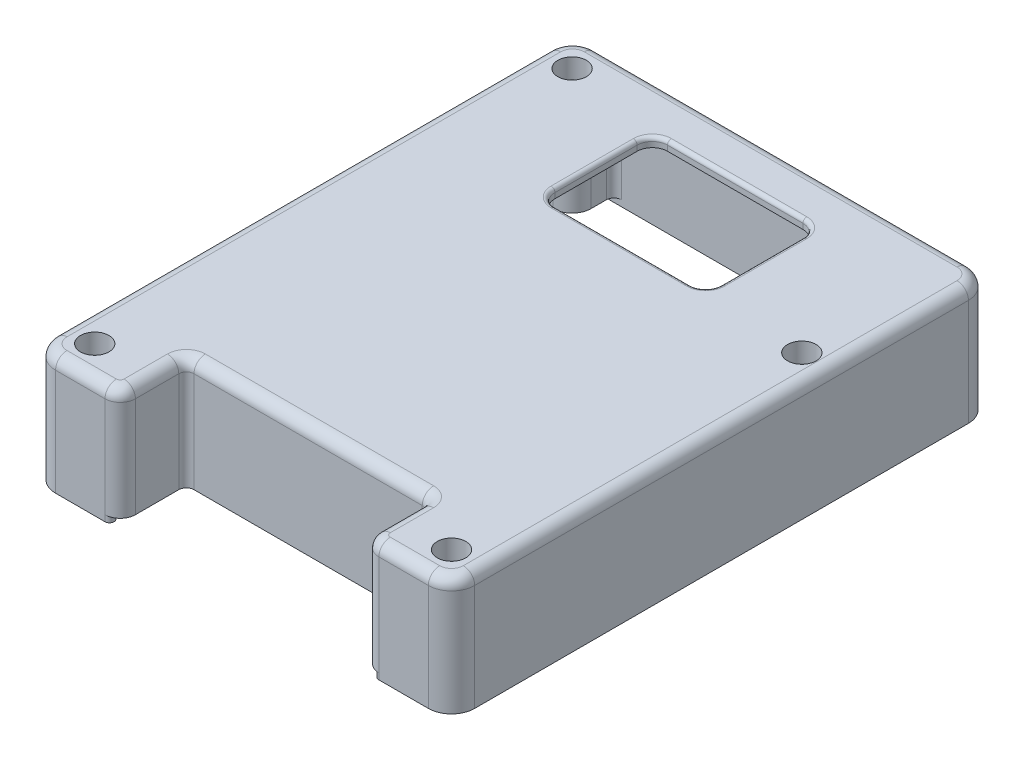
SolidWorks part; units mm, degrees
ref_plane "Front Plane" through (0, 0, 0) normal (0, 0, 1) x (1, 0, 0)
ref_plane "Top Plane" through (0, 0, 0) normal (0, 1, 0) x (1, 0, 0)
ref_plane "Right Plane" through (0, 0, 0) normal (1, 0, 0) x (0, 0, -1)
sketch "Esquisse1" plane through (0, 0, 0) normal (0, 1, 0) x (1, 0, 0)
  line L0 (-20.9, 31.3) -> (-20.9, 33.3)
  line L1 (-19.9, 34.3) -> (23.35, 34.3)
  line L2 (-26.35, 27.8) -> (-26.35, -27.9)
  line L3 (-19.95, -34.3) -> (-18.2, -34.3)
  line L4 (26.35, 31.3) -> (26.35, 17.55)
  line L5 (-26.35, 34.3) -> (26.35, -34.3) construction
  line L6 (-26.35, -34.3) -> (26.35, 34.3) construction
  line L7 (-24.5, 35.5) -> (24.5, 35.5)
  line L8 (-27.55, 32.45) -> (-27.55, -32.45)
  line L9 (-24.5, -35.5) -> (-18, -35.5)
  line L10 (27.55, 32.45) -> (27.55, -32.45)
  line L11 (-23.4, 28.8) -> (-25.35, 28.8)
  line L12 (20.95, -31.4) -> (20.95, -33.3)
  line L13 (23.45, -28.9) -> (25.35, -28.9)
  line L14 (-20.95, -31.4) -> (-20.95, -33.3)
  line L15 (-23.45, -28.9) -> (-25.35, -28.9)
  line L16 (24.05, 16.55) -> (25.35, 16.55)
  line L17 (24.05, 11.55) -> (25.35, 11.55)
  line L18 (26.35, 10.55) -> (26.35, -27.9)
  line L19 (0, 0) -> (0, -34.3) construction
  line L20 (0, -26.8) -> (15, -26.8)
  line L21 (0, -26.8) -> (-15, -26.8)
  line L22 (-16, -27.8) -> (-16, -33.5)
  line L23 (16, -27.8) -> (16, -33.5)
  line L24 (18, -35.5) -> (24.5, -35.5)
  line L25 (18.2, -34.3) -> (19.95, -34.3)
  line L26 (-17.2, -33.3) -> (-17.2, -26.6)
  line L27 (-16.2, -25.6) -> (16.2, -25.6)
  line L28 (17.2, -26.6) -> (17.2, -33.3)
  circle A0 centre (-23.45, -31.4) radius 1.1
  circle A1 centre (23.45, -31.4) radius 1.1
  circle A2 centre (-23.4, 31.3) radius 1.1
  circle A3 centre (24.05, 14.05) radius 1.1
  arc A4 (-23.4, 28.8) -> (-20.9, 31.3) centre (-23.4, 31.3) ccw
  arc A5 (-20.95, -31.4) -> (-23.45, -28.9) centre (-23.45, -31.4) ccw
  arc A6 (23.45, -28.9) -> (20.95, -31.4) centre (23.45, -31.4) ccw
  arc A7 (24.05, 16.55) -> (24.05, 11.55) centre (24.05, 14.05) ccw
  arc A8 (-27.55, -32.45) -> (-24.5, -35.5) centre (-24.5, -32.45) ccw
  arc A9 (24.5, -35.5) -> (27.55, -32.45) centre (24.5, -32.45) ccw
  arc A10 (24.5, 35.5) -> (27.55, 32.45) centre (24.5, 32.45) cw
  arc A11 (-24.5, 35.5) -> (-27.55, 32.45) centre (-24.5, 32.45) ccw
  arc A12 (23.35, 34.3) -> (26.35, 31.3) centre (23.35, 31.3) cw
  arc A13 (-25.35, 28.8) -> (-26.35, 27.8) centre (-25.35, 27.8) ccw
  arc A14 (-20.9, 33.3) -> (-19.9, 34.3) centre (-19.9, 33.3) cw
  arc A15 (25.35, -28.9) -> (26.35, -27.9) centre (25.35, -27.9) ccw
  arc A16 (20.95, -33.3) -> (19.95, -34.3) centre (19.95, -33.3) cw
  arc A17 (-20.95, -33.3) -> (-19.95, -34.3) centre (-19.95, -33.3) ccw
  arc A18 (-25.35, -28.9) -> (-26.35, -27.9) centre (-25.35, -27.9) cw
  arc A19 (25.35, 11.55) -> (26.35, 10.55) centre (25.35, 10.55) cw
  arc A20 (25.35, 16.55) -> (26.35, 17.55) centre (25.35, 17.55) ccw
  arc A21 (-17.2, -33.3) -> (-18.2, -34.3) centre (-18.2, -33.3) cw
  arc A22 (17.2, -33.3) -> (18.2, -34.3) centre (18.2, -33.3) ccw
  arc A23 (16, -33.5) -> (18, -35.5) centre (18, -33.5) ccw
  arc A24 (-16, -33.5) -> (-18, -35.5) centre (-18, -33.5) cw
  arc A25 (-17.2, -26.6) -> (-16.2, -25.6) centre (-16.2, -26.6) cw
  arc A26 (16.2, -25.6) -> (17.2, -26.6) centre (16.2, -26.6) cw
  arc A27 (15, -26.8) -> (16, -27.8) centre (15, -27.8) cw
  arc A28 (-15, -26.8) -> (-16, -27.8) centre (-15, -27.8) ccw
  point P0 (0, 0)
  point P59 (26.35, 11.55)
  point P79 (16, -35.5)
  dimension "D7" = 2.2
  dimension "D8" = 2.2
  dimension "D9" = 2.2
  dimension "D10" = 2.2
  dimension "D19" = 5
  dimension "D20" = 5
  dimension "D21" = 5
  dimension "D22" = 5
  dimension "D23" = 3.05
  dimension "D24" = 3
  dimension "D25" = 1
  dimension "D34" = 1
  dimension "D35" = 2
  dimension "D36" = 1
  dimension "D1" = 52.7
  dimension "D2" = 68.6
  dimension "D3" = 1.2
  dimension "D4" = 1.2
  dimension "D5" = 1.2
  dimension "D6" = 1.2
  dimension "D11" = 2.9
  dimension "D12" = 2.9
  dimension "D13" = 2.9
  dimension "D14" = 2.9
  dimension "D15" = 48.35
  dimension "D16" = 2.3
  dimension "D17" = 2.95
  dimension "D18" = 3
  dimension "D28" = 7.5
  dimension "D29" = 11.55
  dimension "D30" = 11.55
  dimension "D31" = 1.2
  dimension "D32" = 1.2
  dimension "D33" = 1.2
extrude "Boss.-Extru.1" add sketch "Esquisse1" along normal blind 13.5
sketch "Esquisse2" plane through (0, 13.5, 0) normal (0, 1, 0) x (1, 0, 0)
  line L16 (-24.5, -35.5) -> (-18, -35.5)
  line L17 (-16, -33.5) -> (-16, -27.8)
  line L18 (-15, -26.8) -> (15, -26.8)
  line L19 (16, -27.8) -> (16, -33.5)
  line L20 (18, -35.5) -> (24.5, -35.5)
  line L21 (27.55, -32.45) -> (27.55, 32.45)
  line L22 (24.5, 35.5) -> (-24.5, 35.5)
  line L23 (-27.55, 32.45) -> (-27.55, -32.45)
  line L24 (-24.5, -35.5) -> (-18, -35.5)
  line L25 (-16, -33.5) -> (-16, -27.8)
  line L26 (-15, -26.8) -> (15, -26.8)
  line L27 (16, -27.8) -> (16, -33.5)
  line L28 (18, -35.5) -> (24.5, -35.5)
  line L29 (27.55, -32.45) -> (27.55, 32.45)
  line L30 (24.5, 35.5) -> (-24.5, 35.5)
  line L31 (-27.55, 32.45) -> (-27.55, -32.45)
  arc A16 (-27.55, -32.45) -> (-24.5, -35.5) centre (-24.5, -32.45) ccw
  arc A17 (-18, -35.5) -> (-16, -33.5) centre (-18, -33.5) ccw
  arc A18 (-15, -26.8) -> (-16, -27.8) centre (-15, -27.8) ccw
  arc A19 (16, -27.8) -> (15, -26.8) centre (15, -27.8) ccw
  arc A20 (16, -33.5) -> (18, -35.5) centre (18, -33.5) ccw
  arc A21 (24.5, -35.5) -> (27.55, -32.45) centre (24.5, -32.45) ccw
  arc A22 (27.55, 32.45) -> (24.5, 35.5) centre (24.5, 32.45) ccw
  arc A23 (-24.5, 35.5) -> (-27.55, 32.45) centre (-24.5, 32.45) ccw
  arc A24 (-27.55, -32.45) -> (-24.5, -35.5) centre (-24.5, -32.45) ccw
  arc A25 (-18, -35.5) -> (-16, -33.5) centre (-18, -33.5) ccw
  arc A26 (-15, -26.8) -> (-16, -27.8) centre (-15, -27.8) ccw
  arc A27 (16, -27.8) -> (15, -26.8) centre (15, -27.8) ccw
  arc A28 (16, -33.5) -> (18, -35.5) centre (18, -33.5) ccw
  arc A29 (24.5, -35.5) -> (27.55, -32.45) centre (24.5, -32.45) ccw
  arc A30 (27.55, 32.45) -> (24.5, 35.5) centre (24.5, 32.45) ccw
  arc A31 (-24.5, 35.5) -> (-27.55, 32.45) centre (-24.5, 32.45) ccw
  dimension "D1" = 0
extrude "Boss.-Extru.2" add sketch "Esquisse2" along normal blind 1.2
fillet "Congé1" radius 1.5 16 edges at (-27.55, 14.7, 0) (-26.6567, 14.7, -34.6067) (0, 14.7, -35.5) (26.6567, 14.7, -34.6067) (27.55, 14.7, 0) (26.6567, 14.7, 34.6067) (21.25, 14.7, 35.5) (16.5858, 14.7, 34.9142) (16, 14.7, 30.65) (15.7071, 14.7, 27.0929) (0, 14.7, 26.8) (-15.7071, 14.7, 27.0929) (-16, 14.7, 30.65) (-16.5858, 14.7, 34.9142) (-21.25, 14.7, 35.5) (-26.6567, 14.7, 34.6067)
sketch "Esquisse3" plane through (0, 0, 0) normal (0, -1, 0) x (1, 0, 0)
  line L8 (-26.35, 32.45) -> (-26.35, -32.45)
  line L9 (-24.5, -34.3) -> (24.5, -34.3)
  line L10 (26.35, -32.45) -> (26.35, 32.45)
  line L11 (24.5, 34.3) -> (18, 34.3)
  line L12 (17.2, 33.5) -> (17.2, 27.8)
  line L13 (15, 25.6) -> (-15, 25.6)
  line L14 (-17.2, 27.8) -> (-17.2, 33.5)
  line L15 (-18, 34.3) -> (-24.5, 34.3)
  line L16 (-27.55, 32.45) -> (-27.55, -32.45)
  line L17 (-24.5, -35.5) -> (24.5, -35.5)
  line L18 (27.55, -32.45) -> (27.55, 32.45)
  line L19 (24.5, 35.5) -> (18, 35.5)
  line L20 (16, 33.5) -> (16, 27.8)
  line L21 (15, 26.8) -> (-15, 26.8)
  line L22 (-16, 27.8) -> (-16, 33.5)
  line L23 (-18, 35.5) -> (-24.5, 35.5)
  line L24 (-27.55, 32.45) -> (-27.55, -32.45)
  line L25 (-24.5, -35.5) -> (24.5, -35.5)
  line L26 (27.55, -32.45) -> (27.55, 32.45)
  line L27 (24.5, 35.5) -> (18, 35.5)
  line L28 (16, 33.5) -> (16, 27.8)
  line L29 (15, 26.8) -> (-15, 26.8)
  line L30 (-16, 27.8) -> (-16, 33.5)
  line L31 (-18, 35.5) -> (-24.5, 35.5)
  arc A8 (-26.35, -32.45) -> (-24.5, -34.3) centre (-24.5, -32.45) ccw
  arc A9 (24.5, -34.3) -> (26.35, -32.45) centre (24.5, -32.45) ccw
  arc A10 (26.35, 32.45) -> (24.5, 34.3) centre (24.5, 32.45) ccw
  arc A11 (18, 34.3) -> (17.2, 33.5) centre (18, 33.5) ccw
  arc A12 (15, 25.6) -> (17.2, 27.8) centre (15, 27.8) ccw
  arc A13 (-17.2, 27.8) -> (-15, 25.6) centre (-15, 27.8) ccw
  arc A14 (-17.2, 33.5) -> (-18, 34.3) centre (-18, 33.5) ccw
  arc A15 (-24.5, 34.3) -> (-26.35, 32.45) centre (-24.5, 32.45) ccw
  arc A16 (-24.5, 35.5) -> (-27.55, 32.45) centre (-24.5, 32.45) ccw
  arc A17 (-27.55, -32.45) -> (-24.5, -35.5) centre (-24.5, -32.45) ccw
  arc A18 (24.5, -35.5) -> (27.55, -32.45) centre (24.5, -32.45) ccw
  arc A19 (27.55, 32.45) -> (24.5, 35.5) centre (24.5, 32.45) ccw
  arc A20 (18, 35.5) -> (16, 33.5) centre (18, 33.5) ccw
  arc A21 (15, 26.8) -> (16, 27.8) centre (15, 27.8) ccw
  arc A22 (-16, 27.8) -> (-15, 26.8) centre (-15, 27.8) ccw
  arc A23 (-16, 33.5) -> (-18, 35.5) centre (-18, 33.5) ccw
  arc A24 (-24.5, 35.5) -> (-27.55, 32.45) centre (-24.5, 32.45) ccw
  arc A25 (-27.55, -32.45) -> (-24.5, -35.5) centre (-24.5, -32.45) ccw
  arc A26 (24.5, -35.5) -> (27.55, -32.45) centre (24.5, -32.45) ccw
  arc A27 (27.55, 32.45) -> (24.5, 35.5) centre (24.5, 32.45) ccw
  arc A28 (18, 35.5) -> (16, 33.5) centre (18, 33.5) ccw
  arc A29 (15, 26.8) -> (16, 27.8) centre (15, 27.8) ccw
  arc A30 (-16, 27.8) -> (-15, 26.8) centre (-15, 27.8) ccw
  arc A31 (-16, 33.5) -> (-18, 35.5) centre (-18, 33.5) ccw
  dimension "D1" = 0
  dimension "D2" = 1.2
extrude "Boss.-Extru.3" add sketch "Esquisse3" along normal blind 0.8
sketch "Esquisse4" plane through (0, -0.8, 0) normal (0, -1, 0) x (-1, 0, 0)
  line L0 (18, -34.3) -> (24.5, -34.3) construction
  line L1 (18.8331, -34.3) -> (-18.8435, -34.3)
  line L2 (18.8331, -34.3) -> (18.8331, -23.8135)
  line L3 (18.8331, -23.8135) -> (-18.8435, -23.8135)
  line L4 (-18.8435, -34.3) -> (-18.8435, -23.8135)
extrude "Enlèv. mat.-Extru.1" cut sketch "Esquisse4" against normal blind 0.8
fillet "Congé2" radius 0.6 2 edges at (16.167, -0.4, 34.3) (-16.167, -0.4, 34.3)
sketch "Esquisse5" plane through (0, 13.5, 0) normal (0, -1, 0) x (1, 0, 0)
  circle A0 centre (-23.45, 31.4) radius 1.25
  circle A1 centre (23.45, 31.4) radius 1.25
  circle A2 centre (24.05, -14.05) radius 1.25
  circle A3 centre (-23.4, -31.3) radius 1.25
extrude "Enlèv. mat.-Extru.2" cut sketch "Esquisse5" against normal through all
sketch "Esquisse6" plane through (0, 14.7, 0) normal (0, 1, 0) x (1, 0, 0)
  circle A0 centre (-23.4, 31.3) radius 1.875
  circle A1 centre (24.05, 14.05) radius 1.875
  circle A2 centre (23.45, -31.4) radius 1.875
  circle A3 centre (-23.45, -31.4) radius 1.875
  dimension "D1" = 3.75
  dimension "D2" = 3.75
  dimension "D3" = 3.75
  dimension "D4" = 3.75
extrude "Enlèv. mat.-Extru.3" cut sketch "Esquisse6" against normal blind 3.3
fillet "Congé3" radius 0.6 34 edges at (24.7, 13.5, -11.55) (26.0571, 13.5, -11.2571) (26.35, 13.5, 8.675) (26.0571, 13.5, 28.6071) (24.4, 13.5, 28.9) (21.6822, 13.5, 29.6322) (20.95, 13.5, 32.35) (20.6571, 13.5, 34.0071) (19.075, 13.5, 34.3) (17.4929, 13.5, 34.0071) (17.2, 13.5, 29.95) (16.9071, 13.5, 25.8929) (0, 13.5, 25.6) (-16.9071, 13.5, 25.8929) (-17.2, 13.5, 29.95) (-17.4929, 13.5, 34.0071) (-19.075, 13.5, 34.3) (-20.6571, 13.5, 34.0071) (-20.95, 13.5, 32.35) (-21.6822, 13.5, 29.6322) (-24.4, 13.5, 28.9) (-26.0571, 13.5, 28.6071) (-26.35, 13.5, 0.05) (-26.0571, 13.5, -28.5071) (-24.375, 13.5, -28.8) (-21.6322, 13.5, -29.5322) (-20.9, 13.5, -32.3) (-20.6071, 13.5, -34.0071) (1.725, 13.5, -34.3) (25.4713, 13.5, -33.4213) (26.35, 13.5, -24.425) (26.0571, 13.5, -16.8429) (24.7, 13.5, -16.55) (21.55, 13.5, -14.05)
fillet "Congé4" radius 0.7 4 edges at (-23.45, 11.4, 33.275) (23.45, 11.4, 33.275) (-23.4, 11.4, -29.425) (24.05, 11.4, -12.175)
sketch "Esquisse7" plane through (0, 13.5, 0) normal (0, -1, 0) x (1, 0, 0)
  line L0 (0, 0) -> (0, -34.3) construction
  line L1 (23.35, -34.3) -> (-19.9, -34.3) construction
  line L3 (-8.9, -14.55) -> (8.9, -14.55)
  line L4 (-10.9, -16.55) -> (-10.9, -27.35)
  line L5 (-8.9, -29.35) -> (8.9, -29.35)
  line L6 (10.9, -16.55) -> (10.9, -27.35)
  line L7 (-10.9, -14.55) -> (10.9, -29.35) construction
  line L8 (-10.9, -29.35) -> (10.9, -14.55) construction
  arc A0 (8.9, -14.55) -> (10.9, -16.55) centre (8.9, -16.55) cw
  arc A1 (8.9, -29.35) -> (10.9, -27.35) centre (8.9, -27.35) ccw
  arc A2 (-10.9, -27.35) -> (-8.9, -29.35) centre (-8.9, -27.35) ccw
  arc A3 (-8.9, -14.55) -> (-10.9, -16.55) centre (-8.9, -16.55) ccw
  point P5 (0, -21.95)
  dimension "D4" = 2
  dimension "D1" = 12.35
  dimension "D2" = 14.8
  dimension "D3" = 21.8
extrude "Enlèv. mat.-Extru.4" cut sketch "Esquisse7" against normal blind 10
fillet "Congé5" radius 0.5 8 edges at (10.3142, 14.7, -15.1358) (0, 14.7, -14.55) (-10.3142, 14.7, -15.1358) (-10.9, 14.7, -21.95) (-10.3142, 14.7, -28.7642) (0, 14.7, -29.35) (10.3142, 14.7, -28.7642) (10.9, 14.7, -21.95)
